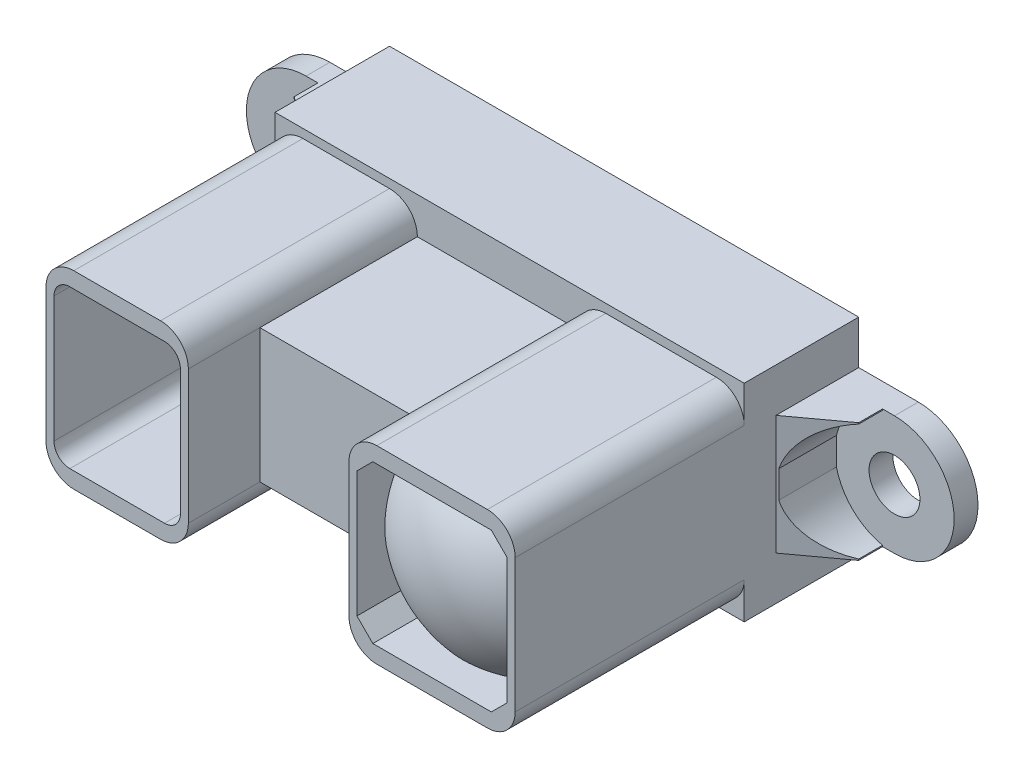
SolidWorks part; units mm, degrees
ref_plane "Front Plane" through (0, 0, 0) normal (0, 0, 1) x (1, 0, 0)
ref_plane "Top Plane" through (0, 0, 0) normal (0, 1, 0) x (1, 0, 0)
ref_plane "Right Plane" through (0, 0, 0) normal (1, 0, 0) x (0, 0, -1)
sketch "Sketch1" plane through (0, 0, 0) normal (0, 0, 1) x (1, 0, 0)
  line L0 (-39.6791, 6.3068) -> (-35.9291, 6.3068)
  line L1 (-35.9291, 9.0568) -> (-6.4291, 9.0568)
  line L2 (-35.9291, 9.0568) -> (-35.9291, 6.3068)
  line L3 (-35.9291, -3.9432) -> (-26.2291, -3.9432)
  line L4 (-6.4291, 9.0568) -> (-6.4291, 6.3068)
  line L5 (-39.6791, -1.1932) -> (-35.9291, -1.1932)
  line L6 (-2.6791, 6.3068) -> (-6.4291, 6.3068)
  line L7 (-2.6791, -1.1932) -> (-6.4291, -1.1932)
  line L8 (-26.2291, -3.9432) -> (-26.2291, -3.0794)
  line L9 (-25.4791, -1.6432) -> (-16.8791, -1.6432)
  line L10 (-16.1291, -3.0794) -> (-16.1291, -3.9432)
  line L11 (-16.1291, -3.9432) -> (-6.4291, -3.9432)
  line L12 (-35.9291, -1.1932) -> (-35.9291, -3.9432)
  line L13 (-6.4291, -1.1932) -> (-6.4291, -3.9432)
  arc A0 (-39.6791, 6.3068) -> (-39.6791, -1.1932) centre (-39.6791, 2.5568) ccw
  arc A1 (-2.6791, -1.1932) -> (-2.6791, 6.3068) centre (-2.6791, 2.5568) ccw
  circle A2 centre (-39.6791, 2.5568) radius 1.6
  circle A3 centre (-2.6791, 2.5568) radius 1.6
  arc A4 (-26.2291, -3.0794) -> (-25.4791, -1.6432) centre (-27.2291, -1.6432) ccw
  arc A5 (-16.8791, -1.6432) -> (-16.1291, -3.0794) centre (-15.1291, -1.6432) ccw
  dimension "D3" = 7.5
  dimension "D4" = 7.5
  dimension "D5" = 3.2
  dimension "D6" = 3.2
  dimension "D16" = 1.75
  dimension "D17" = 1.75
  dimension "D1" = 29.5
  dimension "D2" = 13
  dimension "D7" = 37
  dimension "D8" = 3.75
  dimension "D9" = 6.5
  dimension "D10" = 6.5
  dimension "D11" = 10.1
  dimension "D12" = 9.7
  dimension "D13" = 4.2
extrude "Boss-Extrude1" add sketch "Sketch1" along normal blind 7.2
sketch "Sketch3" plane through (0, -3.9432, 0) normal (0, -1, 0) x (1, 0, 0)
  line L0 (-44.5435, 1.5) -> (-38.9291, 1.5)
  line L1 (-38.9291, 1.5) -> (-38.9291, 3)
  line L2 (-38.9291, 3) -> (-35.9291, 5.2)
  line L3 (-35.9291, 7.2) -> (-35.9291, 0) construction
  line L4 (-35.9291, 5.2) -> (-35.9291, 8.3789)
  line L5 (-35.9291, 8.3789) -> (-44.5435, 8.3789)
  line L6 (-44.5435, 8.3789) -> (-44.5435, 1.5)
  line L7 (-43.4291, 0) -> (-39.6791, 0) construction
  line L8 (-39.6791, 7.2) -> (-35.9291, 7.2) construction
  line L10 (-21.1791, 7.2) -> (-21.1791, 0) construction
  line L11 (-25.4791, 7.2) -> (-16.8791, 7.2) construction
  line L12 (-25.4791, 0) -> (-16.8791, 0) construction
  line L13 (2.1853, 8.3789) -> (2.1853, 1.5)
  line L14 (-6.4291, 8.3789) -> (2.1853, 8.3789)
  line L15 (-6.4291, 5.2) -> (-6.4291, 8.3789)
  line L16 (-3.4291, 3) -> (-6.4291, 5.2)
  line L17 (-3.4291, 1.5) -> (-3.4291, 3)
  line L18 (2.1853, 1.5) -> (-3.4291, 1.5)
  dimension "D1" = 1.5
  dimension "D2" = 2
  dimension "D3" = 1.5
  dimension "D4" = 3
extrude "Cut-Extrude1" cut sketch "Sketch3" against normal through all
sketch "Sketch4" plane through (0, 0, 1.5) normal (0, 0, 1) x (1, 0, 0)
  line L0 (-36.0291, 3.417) -> (-36.0291, 1.6966)
  line L1 (-35.9291, 9.0568) -> (-35.9291, -3.9432) construction
  line L2 (-6.3291, 3.417) -> (-6.3291, 1.6966)
  line L3 (-6.4291, -3.9432) -> (-6.4291, 9.0568) construction
  arc A0 (-36.0291, 3.417) -> (-36.0291, 1.6966) centre (-39.6791, 2.5568) ccw
  arc A1 (-6.3291, 1.6966) -> (-6.3291, 3.417) centre (-2.6791, 2.5568) ccw
  point P10 (-35.9291, 2.5568)
  dimension "D1" = 7.5
  dimension "D2" = 7.5
  dimension "D3" = 180
  dimension "D4" = 0.1
  dimension "D5" = 0.1
extrude "Cut-Extrude2" cut sketch "Sketch4" along normal through all
sketch "Sketch5" plane through (0, 0, 7.2) normal (0, 0, 1) x (1, 0, 0)
  line L0 (-6.4291, 9.0568) -> (-35.9291, 9.0568) construction
  line L1 (-34.1791, 8.5068) -> (-28.7291, 8.5068)
  line L2 (-35.9291, 6.7568) -> (-35.9291, -1.6432)
  line L3 (-34.1791, -3.3932) -> (-28.7291, -3.3932)
  line L4 (-26.9791, 6.7568) -> (-26.9791, -1.6432)
  line L5 (-15.1291, 8.5068) -> (-8.1791, 8.5068)
  line L6 (-16.8791, 6.7568) -> (-16.8791, -1.6432)
  line L7 (-15.1291, -3.3932) -> (-8.1791, -3.3932)
  line L8 (-6.4291, 6.7568) -> (-6.4291, -1.6432)
  line L9 (-34.4291, 7.5068) -> (-28.4791, 7.5068)
  line L10 (-35.4291, 6.5068) -> (-35.4291, -1.3932)
  line L11 (-34.4291, -2.3932) -> (-28.4791, -2.3932)
  line L12 (-27.4791, 6.5068) -> (-27.4791, -1.3932)
  line L13 (-15.3791, 7.5068) -> (-7.9291, 7.5068)
  line L14 (-16.3791, 6.5068) -> (-16.3791, -1.3932)
  line L15 (-15.3791, -2.3932) -> (-7.9291, -2.3932)
  line L16 (-6.9291, 6.5068) -> (-6.9291, -1.3932)
  line L17 (-35.9291, 9.0568) -> (-35.9291, -3.9432) construction
  line L18 (-6.4291, -3.9432) -> (-6.4291, 9.0568) construction
  line L19 (-16.3791, 6.5068) -> (-15.3791, 7.5068)
  line L20 (-7.9291, 7.5068) -> (-6.9291, 6.5068)
  line L21 (-7.9291, -2.3932) -> (-6.9291, -1.3932)
  line L22 (-16.3791, -1.3932) -> (-15.3791, -2.3932)
  arc A0 (-15.1291, 8.5068) -> (-16.8791, 6.7568) centre (-15.1291, 6.7568) ccw
  arc A1 (-8.1791, 8.5068) -> (-6.4291, 6.7568) centre (-8.1791, 6.7568) cw
  arc A2 (-8.1791, -3.3932) -> (-6.4291, -1.6432) centre (-8.1791, -1.6432) ccw
  arc A3 (-16.8791, -1.6432) -> (-15.1291, -3.3932) centre (-15.1291, -1.6432) ccw
  arc A4 (-35.9291, -1.6432) -> (-34.1791, -3.3932) centre (-34.1791, -1.6432) ccw
  arc A5 (-28.7291, -3.3932) -> (-26.9791, -1.6432) centre (-28.7291, -1.6432) ccw
  arc A6 (-28.7291, 8.5068) -> (-26.9791, 6.7568) centre (-28.7291, 6.7568) cw
  arc A7 (-34.1791, 8.5068) -> (-35.9291, 6.7568) centre (-34.1791, 6.7568) ccw
  arc A8 (-35.4291, -1.3932) -> (-34.4291, -2.3932) centre (-34.4291, -1.3932) ccw
  arc A9 (-28.4791, -2.3932) -> (-27.4791, -1.3932) centre (-28.4791, -1.3932) ccw
  arc A10 (-28.4791, 7.5068) -> (-27.4791, 6.5068) centre (-28.4791, 6.5068) cw
  arc A11 (-34.4291, 7.5068) -> (-35.4291, 6.5068) centre (-34.4291, 6.5068) ccw
  point P12 (-16.3791, 7.5068)
  point P13 (-6.9291, -2.3932)
  point P14 (-16.3791, -2.3932)
  point P15 (-6.9291, 7.5068)
  point P24 (-16.8791, 8.5068)
  point P27 (-6.4291, 8.5068)
  point P30 (-6.4291, -3.3932)
  point P35 (-35.9291, -3.3932)
  point P40 (-26.9791, 8.5068)
  point P43 (-35.9291, 8.5068)
  dimension "D9" = 1.75
  dimension "D18" = 1
  dimension "D1" = 11.9
  dimension "D2" = 11.9
  dimension "D3" = 0.55
  dimension "D4" = 0.55
  dimension "D5" = 0
  dimension "D6" = 0
  dimension "D7" = 8.95
  dimension "D8" = 10.45
  dimension "D10" = 0.5
  dimension "D11" = 0.5
  dimension "D12" = 0.5
  dimension "D13" = 0.5
  dimension "D14" = 1
  dimension "D15" = 1
  dimension "D16" = 1
  dimension "D17" = 1
  dimension "D19" = 1
  dimension "D20" = 45
  dimension "D21" = 1
  dimension "D22" = 45
  dimension "D23" = 1
  dimension "D24" = 45
  dimension "D25" = 1
  dimension "D26" = 45
extrude "Boss-Extrude4" add sketch "Sketch5" along normal blind 14.4
sketch "Sketch6" plane through (0, 0, 7.2) normal (0, 0, 1) x (1, 0, 0)
  line L0 (-26.9791, -1.6432) -> (-26.9791, 6.7568) construction
  line L1 (-26.9791, 6.7568) -> (-16.8791, 6.7568)
  line L2 (-26.9791, 6.7568) -> (-26.9791, -1.6432)
  line L3 (-26.9791, -1.6432) -> (-16.8791, -1.6432)
  line L4 (-16.8791, 6.7568) -> (-16.8791, -1.6432)
  line L5 (-16.8791, 6.7568) -> (-16.8791, -1.6432) construction
  circle A0 centre (-39.6791, 2.5568) radius 1.6 construction
  dimension "D1" = 8.4
  dimension "D2" = 4.2
extrude "Boss-Extrude5" add sketch "Sketch6" along normal blind 9.9
ref_axis "Axis1" through (-31.4541, 8.5068, 7.2) along (0, -1, 0)
sketch "Sketch7" plane through (0, 0, 7.2) normal (0, 0, 1) x (1, 0, 0)
  line L0 (-31.4541, 8.5068) -> (-31.4541, -2.3932) construction
  line L1 (-31.4541, 6.5274) -> (-31.4541, -1.2726)
  line L3 (-27.4791, -1.3932) -> (-27.4791, 6.5068) construction
  arc A0 (-31.4541, 6.5274) -> (-31.4541, -1.2726) centre (-31.4541, 2.6274) cw
  dimension "D1" = 3.975
  dimension "D2" = 3.9
revolve "Revolve1" add sketch "Sketch7" angle 180 about axis through (-31.4541, 8.5068, 7.2) along (0, -1, 0)
ref_plane "Plane4" through (-11.6541, 0, 0) normal (1, 0, 0) x (0, 0, -1)
ref_plane "Plane5" through (0, 2.5568, 0) normal (0, 1, 0) x (1, 0, 0)
ref_axis "Axis4" through (-11.6541, 2.5568, 6.48) along (0, 0, 1)
sketch "Sketch11" plane through (-11.6541, 0, 0) normal (1, 0, 0) x (0, 0, -1)
  line L0 (4.0975, 2.5568) -> (-4.0975, 2.5568) construction
  line L1 (-17.85, 9.0068) -> (-17.85, 2.5568)
  line L2 (-21.6, -1.6432) -> (-21.6, 6.7568) construction
  line L3 (-17.85, 2.5568) -> (-21.5228, 2.5568)
  line L4 (-21.6, 8.5068) -> (-7.2, 8.5068) construction
  arc A0 (-17.85, 9.0068) -> (-21.5228, 2.5568) centre (-14.0228, 2.5568) ccw
  dimension "D2" = 15
  dimension "D1" = 3.75
  dimension "D3" = 0.5
revolve "Revolve7" add sketch "Sketch11" angle 360 about axis through (-11.6541, 2.5568, 6.48) along (0, 0, 1)
sketch "Sketch12" plane through (0, 0, 21.6) normal (0, 0, 1) x (1, 0, 0)
  line L0 (-8.1791, 8.5068) -> (-15.1291, 8.5068) construction
  line L1 (-6.4291, -1.6432) -> (-6.4291, 6.7568) construction
  line L2 (-15.1291, -3.3932) -> (-8.1791, -3.3932) construction
  line L3 (-16.8791, 6.7568) -> (-16.8791, -1.6432) construction
  line L4 (-9.1641, 8.5068) -> (-14.1441, 8.5068)
  line L5 (-6.4291, -1.225) -> (-6.4291, 6.3386)
  line L6 (-14.1441, -3.3932) -> (-9.1641, -3.3932)
  line L7 (-16.8791, 6.3386) -> (-16.8791, -1.225)
  arc A8 (-16.8791, 6.3386) -> (-16.8791, -1.225) centre (-11.6541, 2.5568) ccw construction
  arc A9 (-16.8791, 6.3386) -> (-16.8791, -1.225) centre (-11.6541, 2.5568) ccw
  arc A10 (-9.1641, 8.5068) -> (-14.1441, 8.5068) centre (-11.6541, 2.5568) ccw construction
  arc A11 (-9.1641, 8.5068) -> (-14.1441, 8.5068) centre (-11.6541, 2.5568) ccw
  arc A12 (-14.1441, -3.3932) -> (-9.1641, -3.3932) centre (-11.6541, 2.5568) ccw construction
  arc A13 (-14.1441, -3.3932) -> (-9.1641, -3.3932) centre (-11.6541, 2.5568) ccw
  arc A14 (-6.4291, -1.225) -> (-6.4291, 6.3386) centre (-11.6541, 2.5568) ccw construction
  arc A15 (-6.4291, -1.225) -> (-6.4291, 6.3386) centre (-11.6541, 2.5568) ccw
extrude "Cut-Extrude3" cut sketch "Sketch12" against normal blind 4
sketch "Sketch13" [suppressed] plane through (0, 0, 0) normal (0, 0, -1) x (-1, 0, 0)
  line L0 (6.9291, 8.5568) -> (35.4291, 8.5568)
  line L1 (35.4291, 8.5568) -> (35.4291, -3.4432)
  line L2 (35.4291, -3.4432) -> (6.9291, -3.4432)
  line L3 (6.9291, -3.4432) -> (6.9291, 8.5568)
  line L4 (6.4291, 6.3068) -> (6.4291, 9.0568) construction
  line L5 (6.4291, 9.0568) -> (35.9291, 9.0568) construction
  line L6 (16.1291, -3.9432) -> (6.4291, -3.9432) construction
  line L7 (35.9291, 9.0568) -> (35.9291, 6.3068) construction
  dimension "D1" = 0.5
  dimension "D2" = 0.5
  dimension "D3" = 0.5
  dimension "D4" = 0.5
extrude "Cut-Extrude4" [suppressed] cut sketch "Sketch13" against normal blind 3.3
sketch "Sketch14" [suppressed] plane through (0, 0, 3.3) normal (0, 0, -1) x (-1, 0, 0)
  line L0 (26.2291, -3.9432) -> (26.2291, -3.0794) construction
  line L1 (25.4791, -1.6432) -> (16.8791, -1.6432) construction
  line L2 (16.1291, -3.0794) -> (16.1291, -3.9432) construction
  line L3 (26.2291, -3.9432) -> (26.2291, -3.0794)
  line L4 (25.4791, -1.6432) -> (16.8791, -1.6432)
  line L5 (16.1291, -3.0794) -> (16.1291, -3.9432)
  line L6 (16.1291, -3.9432) -> (16.1291, -8.8432)
  line L7 (17.1291, -9.8432) -> (25.2291, -9.8432)
  line L8 (26.2291, -8.8432) -> (26.2291, -3.9432)
  line L9 (6.4291, 9.0568) -> (35.9291, 9.0568) construction
  arc A0 (25.4791, -1.6432) -> (26.2291, -3.0794) centre (27.2291, -1.6432) ccw construction
  arc A1 (16.1291, -3.0794) -> (16.8791, -1.6432) centre (15.1291, -1.6432) ccw construction
  arc A2 (25.4791, -1.6432) -> (26.2291, -3.0794) centre (27.2291, -1.6432) ccw
  arc A3 (16.1291, -3.0794) -> (16.8791, -1.6432) centre (15.1291, -1.6432) ccw
  arc A4 (25.2291, -9.8432) -> (26.2291, -8.8432) centre (25.2291, -8.8432) ccw
  arc A5 (16.1291, -8.8432) -> (17.1291, -9.8432) centre (17.1291, -8.8432) ccw
  dimension "D2" = 1
  dimension "D1" = 18.9
extrude "Boss-Extrude6" [suppressed] add sketch "Sketch14" against normal blind 1.2
ref_plane "Plane6" [suppressed] through (-21.1791, 0, 0) normal (-1, 0, 0) x (0, 0, 1)
sketch "Sketch15" [suppressed] plane through (-21.1791, 0, 0) normal (-1, 0, 0) x (0, 0, 1)
  line L0 (6.5, -2.1432) -> (4.5, -2.1432)
  line L1 (4.5, -2.1432) -> (4.5, -9.7432)
  line L2 (4.5, -9.7432) -> (7.1, -9.7432)
  line L3 (7.1, -9.7432) -> (7.1, -8.2432)
  line L4 (7.1, -8.2432) -> (8.1, -8.2432) construction
  line L5 (8.1, -8.2432) -> (8.1, -9.7432)
  line L6 (8.1, -9.7432) -> (9.3, -9.7432)
  line L7 (9.3, -9.7432) -> (9.3, -3.7432)
  line L8 (9.3, -3.7432) -> (8.1, -3.7432)
  line L9 (8.1, -3.7432) -> (6.5, -2.1432)
  line L10 (4.5, -8.8432) -> (4.5, -3.9432) construction
  line L11 (4.5, -9.8432) -> (3.3, -9.8432) construction
  arc A0 (8.1, -8.2432) -> (7.1, -8.2432) centre (7.6, -8.2432) ccw
  point P2 (7.6, -8.2432)
  dimension "D1" = 4.8
  dimension "D2" = 6
  dimension "D3" = 7.6
  dimension "D4" = 1.6
  dimension "D5" = 1.7
  dimension "D6" = 0
  dimension "D7" = 0.1
  dimension "D8" = 1
  dimension "D9" = 1.5
  dimension "D10" = 2
  dimension "D11" = 1.2
extrude "Boss-Extrude7" [suppressed] add sketch "Sketch15" along normal blind 3.95 and the other way blind 3.95
sketch "Sketch16" [suppressed] plane through (0, -9.7432, 0) normal (0, -1, 0) x (1, 0, 0)
  line L0 (-17.2291, 9.3) -> (-25.1291, 9.3) construction
  line L1 (-24.6291, 8.8) -> (-17.7291, 8.8)
  line L2 (-24.6291, 8.8) -> (-24.6291, 5)
  line L3 (-24.6291, 5) -> (-17.7291, 5)
  line L4 (-17.7291, 8.8) -> (-17.7291, 5)
  line L5 (-25.1291, 4.5) -> (-25.1291, 7.1) construction
  line L6 (-17.2291, 4.5) -> (-25.1291, 4.5) construction
  line L7 (-17.2291, 8.1) -> (-17.2291, 9.3) construction
  dimension "D1" = 0.5
  dimension "D2" = 0.5
  dimension "D3" = 0.5
  dimension "D4" = 0.5
extrude "Cut-Extrude5" [suppressed] cut sketch "Sketch16" against normal blind 5.5
ref_point "Point2" [suppressed]
sketch "Sketch18" [suppressed] plane through (0, -4.2432, 0) normal (0, -1, 0) x (1, 0, 0)
  circle A0 centre (-21.1791, 6.9) radius 0.5
  circle A1 centre (-19.1791, 6.9) radius 0.5
  circle A2 centre (-23.1791, 6.9) radius 0.5
  dimension "D1" = 2
  dimension "D2" = 2
extrude "Boss-Extrude8" [suppressed] add sketch "Sketch18" along normal blind 5.25
fillet "Fillet1" [suppressed] radius 0.5
